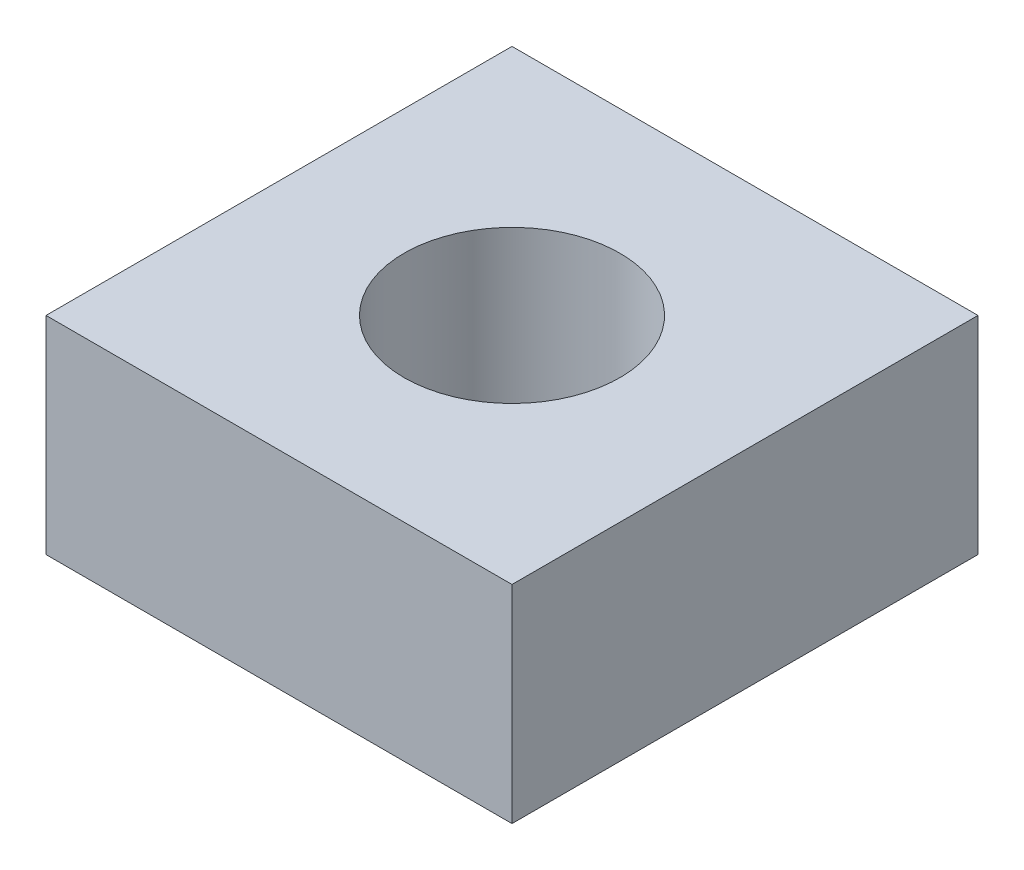
SolidWorks part; units mm, degrees
ref_plane "Front" through (0, 0, 0) normal (0, 0, 1) x (1, 0, 0)
ref_plane "Top" through (0, 0, 0) normal (0, 1, 0) x (1, 0, 0)
ref_plane "Right" through (0, 0, 0) normal (1, 0, 0) x (0, 0, -1)
sketch "Sketch1" plane through (0, 0, 0) normal (0, 1, 0) x (1, 0, 0)
  line L1 (-2.7, -2.7) -> (2.7, -2.7)
  line L2 (-2.7, -2.7) -> (-2.7, 2.7)
  line L3 (-2.7, 2.7) -> (2.7, 2.7)
  line L4 (2.7, -2.7) -> (2.7, 2.7)
  line L5 (-2.7, -2.7) -> (2.7, 2.7) construction
  line L6 (-2.7, 2.7) -> (2.7, -2.7) construction
  point P0 (0, 0)
  dimension "D1" = 5.4
extrude "Boss-Extrude1" add sketch "Sketch1" along normal blind 2.4
hole_wizard "M3x0.5 Tapped Hole1" positions "Sketch3" profile "Sketch4" tap size "M3x0.5" standard "ANSI Metric" end condition through all
sketch "Sketch3" plane through (0, 2.4, 0) normal (0, 1, 0) x (1, 0, 0)
  point P0 (0, 0)
sketch "Sketch4" plane through (0, 2.4, 0) normal (1, 0, 0) x (0, 0, 1)
  line L0 (0, 0) -> (0, 2.4)
  line L1 (0, 2.4) -> (1.25, 2.4)
  line L2 (1.25, 2.4) -> (1.25, 0)
  line L5 (1.25, 0) -> (0, 0)
  line L11 (0, -6.35) -> (0, 107.95) construction
  dimension "Thru Tap Drill Dia." = 2.5
  dimension "Thru Tap Drill Depth" = 2.4
cosmetic thread "Hole Thread1" parameters "D2"=3
